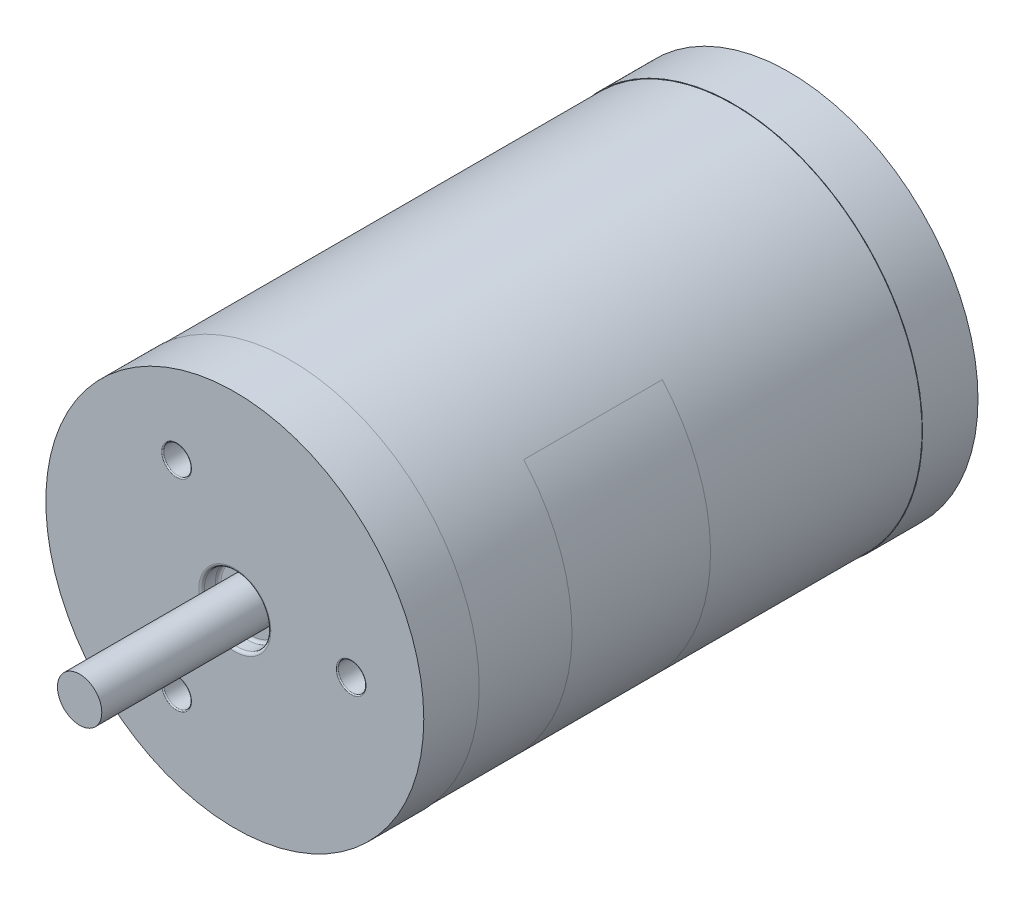
SolidWorks part; units mm, degrees
ref_plane "Alzado" through (0, 0, 0) normal (0, 0, 1) x (1, 0, 0)
ref_plane "Planta" through (0, 0, 0) normal (0, 1, 0) x (1, 0, 0)
ref_plane "Vista lateral" through (0, 0, 0) normal (1, 0, 0) x (0, 0, -1)
sketch "Croquis1" plane through (0, 0, 0) normal (0, 0, 1) x (1, 0, 0)
  circle A0 centre (0, 0) radius 34
  dimension "D1" = 68
extrude "Saliente-Extruir1" add sketch "Croquis1" along normal mid plane 100
sketch "Croquis2" plane through (0, 0, 50) normal (0, 0, 1) x (1, 0, 0)
  circle A0 centre (0, 0) radius 4
  dimension "D1" = 8
extrude "Saliente-Extruir2" add sketch "Croquis2" along normal blind 28
sketch "Croquis3" plane through (0, 0, 50) normal (0, 0, 1) x (1, 0, 0)
  circle A0 centre (0, 0) radius 21 construction
  circle A1 centre (21, 0) radius 2.5
  circle A2 centre (-10.5, -18.1865) radius 2.5
  circle A3 centre (-10.5, 18.1865) radius 2.5
  point P12 (0, 0)
  dimension "D1" = 42
  dimension "D2" = 5
  dimension "D3" = 3
extrude "Cortar-Extruir1" cut sketch "Croquis3" against normal blind 5
sketch "Croquis4" plane through (0, 0, -50) normal (0, 0, -1) x (-1, 0, 0)
  circle A0 centre (0, 0) radius 15
  dimension "D1" = 30
extrude "Saliente-Extruir3" add sketch "Croquis4" along normal blind 10.5
sketch "Croquis5" plane through (0, 0, -50) normal (0, 0, -1) x (-1, 0, 0)
  line L0 (-30, 0) -> (0, 0) construction
  circle A0 centre (-30, 0) radius 2
  circle A1 centre (0, 0) radius 30 construction
  circle A2 centre (30, 0) radius 2
  dimension "D1" = 4
  dimension "D2" = 60
extrude "Cortar-Extruir2" cut sketch "Croquis5" against normal blind 10.5
sketch "Croquis6" plane through (0, 0, 50) normal (0, 0, 1) x (1, 0, 0)
  circle A0 centre (0, 0) radius 34.1
  circle A1 centre (0, 0) radius 34 construction
  circle A2 centre (21, 0) radius 2.5 construction
  circle A3 centre (-10.5, -18.1865) radius 2.5 construction
  circle A4 centre (-10.5, 18.1865) radius 2.5 construction
  circle A5 centre (21, 0) radius 2.5
  circle A6 centre (-10.5, -18.1865) radius 2.5
  circle A7 centre (-10.5, 18.1865) radius 2.5
  dimension "D1" = 0.1
extrude "Saliente-Extruir4" add sketch "Croquis6" against normal blind 10
mirror "Simetría1" about plane through (0, 0, 0) normal (0, 0, 1) of "Saliente-Extruir4"
fillet "Redondeo1" radius 1 1 edges at (-15, 0, -60.5)
sketch "Croquis7" plane through (0, 0, 0) normal (1, 0, 0) x (0, 0, -1)
  line L1 (-23.1573, -24.8743) -> (1.8427, -24.8743)
  line L2 (-23.1573, -24.8743) -> (-23.1573, 24.8743)
  line L3 (-23.1573, 24.8743) -> (1.8427, 24.8743)
  line L4 (1.8427, -24.8743) -> (1.8427, 24.8743)
  line L5 (-23.1573, -24.8743) -> (1.8427, 24.8743) construction
  line L6 (-23.1573, 24.8743) -> (1.8427, -24.8743) construction
  point P0 (-10.6573, 0)
  dimension "D1" = 25
wrap "Envolver1" sketch "Croquis7" wrap type scribe source sketch "Croquis7" face at (34, 0, 40)
ref_plane "Plano1" through (0, -34, 0) normal (0, -1, 0) x (-1, 0, 0)
sketch "Croquis8" plane through (0, -34, 0) normal (0, -1, 0) x (-1, 0, 0)
  line L1 (9.3304, -43.5501) -> (-9.3304, -43.5501)
  line L2 (9.3304, -43.5501) -> (9.3304, -33.5047)
  line L3 (9.3304, -33.5047) -> (-9.3304, -33.5047)
  line L4 (-9.3304, -43.5501) -> (-9.3304, -33.5047)
  line L5 (9.3304, -43.5501) -> (-9.3304, -33.5047) construction
  line L6 (9.3304, -33.5047) -> (-9.3304, -43.5501) construction
  point P0 (0, -38.5274)
extrude "Cortar-Extruir3" cut sketch "Croquis8" against normal blind 5 and the other way blind 5
sketch "Croquis9" plane through (0, 0, -50) normal (0, 0, -1) x (-1, 0, 0)
  circle A1 centre (30, 0) radius 2
  circle A2 centre (30, 0) radius 2
  circle A3 centre (-30, 0) radius 2
  circle A4 centre (-30, 0) radius 2
  dimension "D1" = 0
  dimension "D2" = 0
extrude "Cortar-Extruir4" cut sketch "Croquis9" against normal blind 5
sketch "Croquis10" plane through (0, 0, 50) normal (0, 0, 1) x (1, 0, 0)
  circle A0 centre (0, 0) radius 4 construction
  circle A1 centre (0, 0) radius 4
  circle A2 centre (0, 0) radius 6
  dimension "D1" = 2
extrude "Cortar-Extruir5" cut sketch "Croquis10" against normal blind 3
fillet "Redondeo2" radius 0.5 1 edges at (6, 0, 50)
fillet "Redondeo3" radius 0.5 1 edges at (6, 0, 47)
fillet "Redondeo4" radius 0.2 3 edges at (-8, 18.1865, 50) (23.5, 0, 50) (-8, -18.1865, 50)
